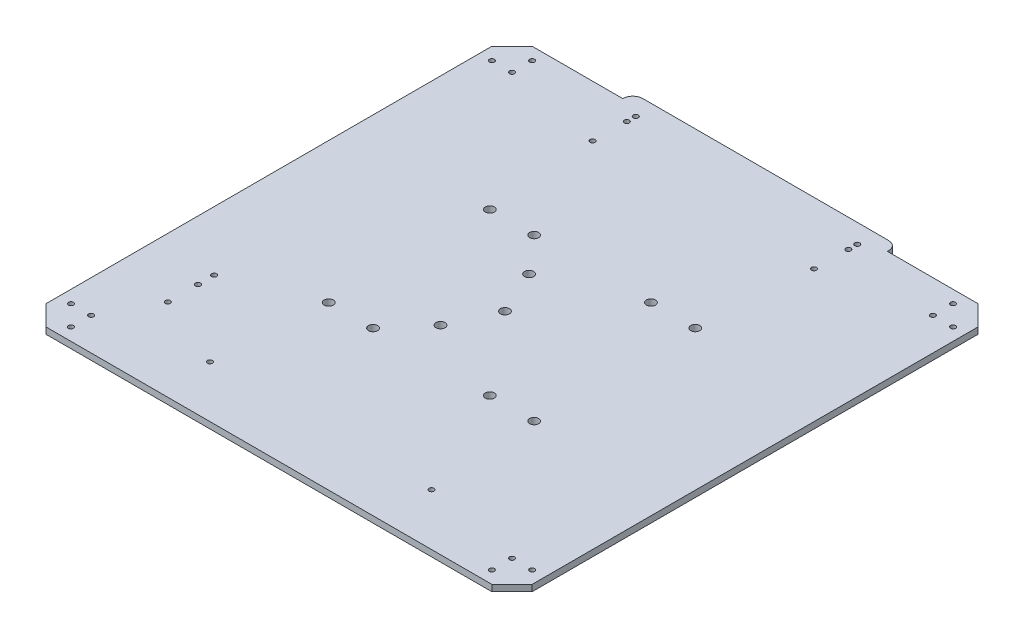
SolidWorks part; units mm, degrees
material "6061-T6 (SS)"
ref_plane "Front Plane" through (0, 0, 0) normal (0, 0, 1) x (1, 0, 0)
ref_plane "Top Plane" through (0, 0, 0) normal (0, 1, 0) x (1, 0, 0)
ref_plane "Right Plane" through (0, 0, 0) normal (1, 0, 0) x (0, 0, -1)
sketch "Sketch1" plane through (0, 0, 0) normal (0, 1, 0) x (1, 0, 0)
  line L0 (-120.7, 120.7) -> (120.7, -120.7) construction
  line L1 (-110.7, 120.7) -> (110.7, 120.7)
  line L2 (-120.7, 110.7) -> (-120.7, -110.7)
  line L3 (-110.7, -120.7) -> (110.7, -120.7)
  line L4 (120.7, 110.7) -> (120.7, -110.7)
  line L5 (110.7, -120.7) -> (120.7, -110.7)
  line L6 (110.7, 120.7) -> (120.7, 110.7)
  line L7 (-120.7, 110.7) -> (-110.7, 120.7)
  line L8 (-120.7, -110.7) -> (-110.7, -120.7)
  point P2 (-120.7, -120.7)
  point P3 (120.7, 120.7)
  dimension "D1" = 241.4
  dimension "D2" = 241.4
extrude "Boss-Extrude1" add sketch "Sketch1" along normal blind 3.175
sketch "Sketch2" plane through (0, 3.175, 0) normal (0, 1, 0) x (1, 0, 0)
  circle A0 centre (-51, -40) radius 1.5
  circle A2 centre (-29, -40) radius 2.25
  circle A5 centre (-51, 40) radius 1.5
  circle A6 centre (-29, 40) radius 2.25
  circle A9 centre (29, 40) radius 2.25
  circle A10 centre (51, 40) radius 2.25
  circle A14 centre (29, -40) radius 2.25
  circle A15 centre (51, -40) radius 2.25
  circle A16 centre (-3.5, 0) radius 2.25
  circle A17 centre (-13.5, 22) radius 2.25
  circle A18 centre (-13.5, -22) radius 2.25
  dimension "D1" = 3
  dimension "D2" = 4.5
extrude "Cut-Extrude1" cut sketch "Sketch2" against normal through all
hole_wizard "M3x0.5 Tapped Hole1" positions "Sketch4" profile "Sketch3" tap size "M3x0.5" standard "Ansi Metric" end condition through all
sketch "Sketch4" plane through (0, 3.175, 0) normal (0, 1, 0) x (-1, 0, 0)
  line L0 (110.7, 120.7) -> (-110.7, 120.7) construction
  line L1 (120.7, -110.7) -> (120.7, 110.7) construction
  line L2 (-110.7, -120.7) -> (110.7, -120.7) construction
  line L3 (-120.7, 110.7) -> (-120.7, -110.7) construction
  point P0 (114.5, -104.5)
  point P1 (104.5, -114.5)
  point P3 (-104.5, -114.5)
  point P5 (-114.5, -104.5)
  point P7 (-114.5, 104.5)
  point P9 (-104.5, 114.5)
  point P11 (104.5, 114.5)
  point P13 (114.5, 104.5)
  point P32 (-104.5, 104.5)
  point P34 (-104.5, -104.5)
  point P36 (104.5, -104.5)
  point P38 (104.5, 104.5)
  dimension "D1" = 16.2
  dimension "D2" = 6.2
  dimension "D3" = 6.2
  dimension "D4" = 16.2
  dimension "D5" = 16.2
  dimension "D6" = 6.2
  dimension "D7" = 6.2
  dimension "D8" = 16.2
  dimension "D9" = 209
  dimension "D10" = 209
sketch "Sketch3" plane through (-114.5, 3.175, -104.5) normal (1, 0, 0) x (0, 0, 1)
  line L0 (0, 0) -> (0, 3.175)
  line L1 (0, 3.175) -> (1.25, 3.175)
  line L2 (1.25, 3.175) -> (1.25, 0)
  line L5 (1.25, 0) -> (0, 0)
  line L11 (0, -6.35) -> (0, 107.95) construction
  dimension "Thru Tap Drill Dia." = 2.5
  dimension "Thru Tap Drill Depth" = 3.175
cosmetic thread "Hole Thread1" parameters "D2"=3
cosmetic thread "Hole Thread2" parameters "D2"=3
cosmetic thread "Hole Thread3" parameters "D2"=3
cosmetic thread "Hole Thread4" parameters "D2"=3
cosmetic thread "Hole Thread5" parameters "D2"=3
cosmetic thread "Hole Thread6" parameters "D2"=3
cosmetic thread "Hole Thread7" parameters "D2"=3
cosmetic thread "Hole Thread8" parameters "D2"=3
cosmetic thread "Hole Thread9" parameters "D2"=3
cosmetic thread "Hole Thread10" parameters "D2"=3
cosmetic thread "Hole Thread11" parameters "D2"=3
cosmetic thread "Hole Thread12" parameters "D2"=3
sketch "Sketch5" plane through (0, 3.175, 0) normal (0, 1, 0) x (1, 0, 0)
  circle A0 centre (-55, 95) radius 1.25
  circle A1 centre (55, 95) radius 1.25
  circle A2 centre (-55, -95) radius 1.25
  circle A3 centre (55, -95) radius 1.25
  dimension "D1" = 2.5
extrude "Cut-Extrude2" cut sketch "Sketch5" against normal through all
sketch "Sketch6" plane through (0, 3.175, 0) normal (0, 1, 0) x (1, 0, 0)
  line L0 (-110.7, -120.7) -> (110.7, -120.7) construction
  line L1 (-120.7, 110.7) -> (-120.7, -110.7) construction
  circle A0 centre (-91.2, -64.7) radius 1.25
  circle A1 centre (-91.2, -56.7) radius 1.25
  circle A2 centre (-91.2, -79.7) radius 1.25
  dimension "D3" = 2.5
  dimension "D1" = 56
  dimension "D2" = 29.5
  dimension "D4" = 8
  dimension "D5" = 15
extrude "Cut-Extrude3" cut sketch "Sketch6" against normal blind 10
hole_wizard "M4 Clearance Hole1" positions "Sketch8" profile "Sketch7" hole size "M4" standard "ANSI Metric"
sketch "Sketch8" plane through (0, 3.175, 0) normal (0, 1, 0) x (-1, 0, 0)
  point P0 (51, -40)
  point P1 (51, 40)
sketch "Sketch7" plane through (-51, 3.175, -40) normal (1, 0, 0) x (0, 0, 1)
  line L0 (0, 0) -> (0, 11.3519)
  line L1 (0, 11.3519) -> (2.25, 10)
  line L2 (2.25, 10) -> (2.25, 0)
  line L5 (2.25, 0) -> (0, 0)
  line L10 (0, 11.3519) -> (-2.25, 10) construction
  line L11 (0, -6.35) -> (0, 107.95) construction
  dimension "Hole Dia." = 4.5
  dimension "Hole Depth" = 10
  dimension "Drill Angle" = 118
hole_wizard "M3x0.5 Tapped Hole2" positions "Sketch14" profile "Sketch13" tap size "M3x0.5" standard "ANSI Metric" end condition through all
sketch "Sketch14" plane through (0, 3.175, 0) normal (0, 1, 0) x (-1, 0, 0)
  point P0 (-55.1885, -111.8444)
  point P2 (54.8115, -111.8444)
  point P3 (-55.1885, -111.8444)
  point P5 (-55.1885, -116.2672)
  point P7 (-55.1885, -116.2672)
  point P9 (54.8115, -116.2672)
  dimension "D1" = 110
cosmetic thread "Hole Thread13" parameters "D2"=3
cosmetic thread "Hole Thread14" parameters "D2"=3
cosmetic thread "Hole Thread15" parameters "D2"=3
cosmetic thread "Hole Thread16" parameters "D2"=3
cosmetic thread "Hole Thread19" parameters "D2"=3
cosmetic thread "Hole Thread20" parameters "D2"=3
sketch "Sketch13" plane through (55.1885, 3.175, -111.8444) normal (1, 0, 0) x (0, 0, 1)
  line L0 (0, 0) -> (0, 3.175)
  line L1 (0, 3.175) -> (1.25, 3.175)
  line L2 (1.25, 3.175) -> (1.25, 0)
  line L5 (1.25, 0) -> (0, 0)
  line L11 (0, -6.35) -> (0, 107.95) construction
  dimension "Thru Tap Drill Dia." = 2.5
  dimension "Thru Tap Drill Depth" = 3.175
sketch "Sketch15" plane through (0, 0, -120.7) normal (0, 0, -1) x (-1, 0, 0)
  line L0 (-110.7, 0) -> (110.7, 0) construction
  line L1 (65.7, 0) -> (-65.7, 0)
  line L2 (65.7, 0) -> (65.7, 3.175)
  line L3 (65.7, 3.175) -> (-65.7, 3.175)
  line L4 (-65.7, 0) -> (-65.7, 3.175)
  line L5 (-110.7, 3.175) -> (110.7, 3.175) construction
  line L6 (110.7, 3.175) -> (110.7, 0) construction
  point P8 (110.7, 1.5875)
  dimension "D1" = 45
  dimension "D2" = 45
extrude "Boss-Extrude2" add sketch "Sketch15" along normal blind 5
fillet "Fillet1" radius 5 1 edges at (-65.7, 1.5875, -125.7)
fillet "Fillet2" radius 5 1 edges at (65.7, 1.5875, -125.7)
